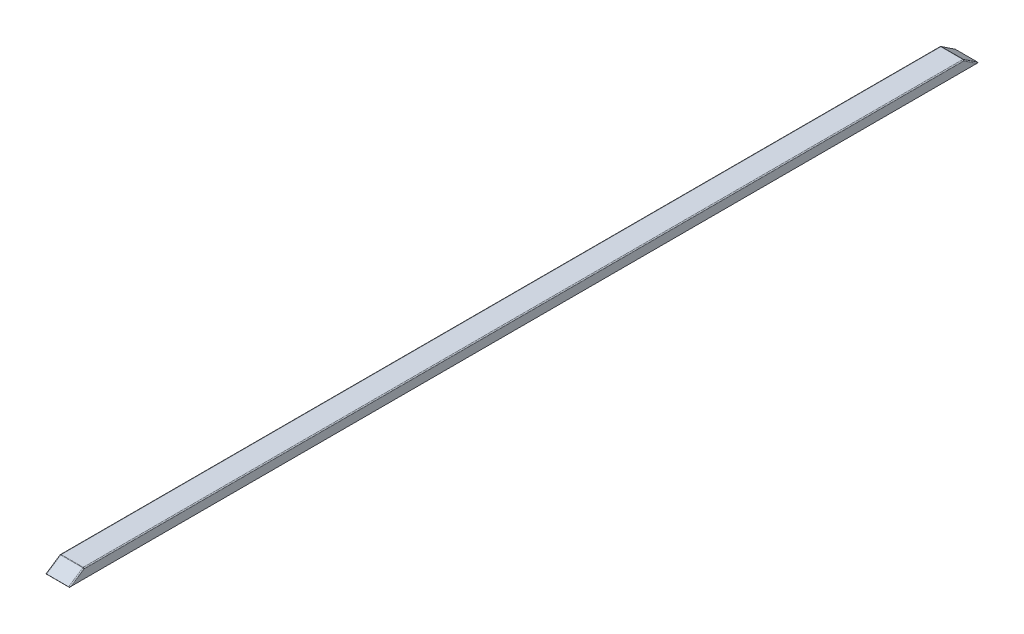
SolidWorks part; units mm, degrees
ref_plane "Front Plane" through (0, 0, 0) normal (0, 0, 1) x (1, 0, 0)
ref_plane "Top Plane" through (0, 0, 0) normal (0, 1, 0) x (1, 0, 0)
ref_plane "Right Plane" through (0, 0, 0) normal (1, 0, 0) x (0, 0, -1)
sketch "Sketch1" plane through (0, 0, 0) normal (0, 0, 1) x (1, 0, 0)
  line L0 (0, 0) -> (0, 20)
  line L1 (0, 20) -> (50, 20)
  line L2 (50, 20) -> (50, 0)
  line L3 (2, 0) -> (2, 18)
  line L4 (2, 18) -> (48, 18)
  line L5 (48, 18) -> (48, 0)
  line L6 (0, 0) -> (2, 0)
  line L7 (48, 0) -> (50, 0)
  dimension "D1" = 50
  dimension "D2" = 20
  dimension "D3" = 2
extrude "Boss-Extrude1" add sketch "Sketch1" along normal blind 1900
fillet "Fillet1" radius 2 4 edges at (48, 18, 950) (2, 18, 950) (0, 20, 950) (50, 20, 950)
sketch "Sketch2" plane through (50, 0, 0) normal (1, 0, 0) x (0, 0, -1)
  line L0 (0, 0) -> (-30, 20)
  line L1 (-1900, 20) -> (0, 20) construction
  line L2 (-30, 20) -> (0, 20)
  line L3 (0, 20) -> (0, 0)
  line L4 (-1900, 0) -> (-1870, 20)
  line L5 (-1870, 20) -> (-1900, 20)
  line L6 (-1900, 20) -> (-1900, 0)
  dimension "D1" = 30
  dimension "D2" = 30
extrude "Cut-Extrude1" cut sketch "Sketch2" against normal through all both and the other way through all
sketch "Sketch5" plane through (0, 0, 0) normal (0, 0.8321, -0.5547) x (1, 0, 0)
  line L0 (0, 0) -> (50, 0)
  line L8 (46, -32.45) -> (4, -32.45)
  line L9 (2, -28.8444) -> (2, 0)
  line L10 (2, 0) -> (0, 0)
  line L11 (0, 0) -> (0, -32.45)
  line L12 (2, -36.0555) -> (48, -36.0555)
  line L13 (50, -32.45) -> (50, 0)
  line L14 (50, 0) -> (48, 0)
  line L15 (48, 0) -> (48, -28.8444)
  line L19 (0, 0) -> (0, -32.45)
  line L20 (2, -36.0555) -> (48, -36.0555)
  line L21 (50, -32.45) -> (50, 0)
  ellipse E4 centre (46, -28.8444) end of major axis (46, -32.45) minor radius 2 (46, -32.45) -> (48, -28.8444) ccw
  ellipse E5 centre (4, -28.8444) end of major axis (4, -32.45) minor radius 2 (2, -28.8444) -> (4, -32.45) ccw
  ellipse E6 centre (2, -32.45) end of major axis (2, -28.8444) minor radius 2 (0, -32.45) -> (2, -36.0555) ccw
  ellipse E7 centre (48, -32.45) end of major axis (48, -28.8444) minor radius 2 (48, -36.0555) -> (50, -32.45) ccw
  ellipse E10 centre (2, -32.45) end of major axis (2, -28.8444) minor radius 2 (0, -32.45) -> (2, -36.0555) ccw
  ellipse E11 centre (48, -32.45) end of major axis (48, -28.8444) minor radius 2 (48, -36.0555) -> (50, -32.45) ccw
  dimension "D1" = 0
extrude "Boss-Extrude2" add sketch "Sketch5" against normal blind 1
sketch "Sketch6" plane through (0, 876.9231, 584.6154) normal (0, 0.8321, 0.5547) x (1, 0, 0)
  line L0 (0, -1580.8956) -> (50, -1580.8956)
  line L8 (48, -1580.8956) -> (50, -1580.8956)
  line L9 (50, -1580.8956) -> (50, -1548.4456)
  line L10 (48, -1544.84) -> (2, -1544.84)
  line L11 (0, -1548.4456) -> (0, -1580.8956)
  line L12 (0, -1580.8956) -> (2, -1580.8956)
  line L13 (2, -1580.8956) -> (2, -1552.0511)
  line L14 (4, -1548.4456) -> (46, -1548.4456)
  line L15 (48, -1552.0511) -> (48, -1580.8956)
  line L17 (50, -1580.8956) -> (50, -1548.4456)
  line L18 (48, -1544.84) -> (2, -1544.84)
  line L19 (0, -1548.4456) -> (0, -1580.8956)
  ellipse E4 centre (48, -1548.4456) end of major axis (48, -1544.84) minor radius 2 (50, -1548.4456) -> (48, -1544.84) ccw
  ellipse E5 centre (2, -1548.4456) end of major axis (2, -1544.84) minor radius 2 (2, -1544.84) -> (0, -1548.4456) ccw
  ellipse E6 centre (4, -1552.0511) end of major axis (4, -1555.6567) minor radius 2 (4, -1548.4456) -> (2, -1552.0511) ccw
  ellipse E7 centre (46, -1552.0511) end of major axis (46, -1555.6567) minor radius 2 (48, -1552.0511) -> (46, -1548.4456) ccw
  ellipse E8 centre (48, -1548.4456) end of major axis (48, -1544.84) minor radius 2 (50, -1548.4456) -> (48, -1544.84) ccw
  ellipse E9 centre (2, -1548.4456) end of major axis (2, -1544.84) minor radius 2 (2, -1544.84) -> (0, -1548.4456) ccw
  dimension "D1" = 0
extrude "Boss-Extrude3" add sketch "Sketch6" against normal blind 1
fillet "Fillet2" radius 2 5 edges at (0, 9, 1886.5) (0.5858, 19.4142, 1870.8787) (50, 9, 1886.5) (49.4142, 19.4142, 1870.8787) (25, 20, 1870)
fillet "Fillet3" radius 2 5 edges at (0, 9, 13.5) (0.5858, 19.4142, 29.1213) (50, 9, 13.5) (49.4142, 19.4142, 29.1213) (25, 20, 30)
equation "\"totalWidth\"=1930"
equation "\"D1@Boss-Extrude1\"= \"boxWidth\" - 30"
equation "\"CarBeamWidth\"=700.0"
equation "\"WheelWidth\"=650.0"
equation "\"Wheel_FrontBoxDistance\"=1390.0"
equation "\"boxLength\"=5100.0"
equation "\"boxWidth\"=1930.0"
equation "\"MetalSheet_3mm_length\"=5030.0"
equation "\"MetalSheet_3mm_width\"=1923.0"
equation "\"MetalSheet_3mm_FloorCut_L_length\"=1764.0"
equation "\"MetalSheet_3mm_FloorCut_L_disdance\"=1665.0"
equation "\"MetalSheet_3mm_FloorCut_R_length\"=1764.0"
equation "\"MetalSheet_3mm_FloorCut_R_disdance\"=1665.0"
equation "\"indoorHeight\"=1940.0"
equation "\"indoorHeight_para\"=25.0"
equation "\"rearLightHeight_para\"=265.0"
equation "\"doorColumnBar_A_FR_3mm_length_Cut\"=2310.0"
equation "\"A\"=0.0"
equation "\"haveDoor_R\"=1"
equation "\"side_door_bottom_R_3mm_length\"=1934.0"
equation "\"side_door_bottom_R_3mm_toFrontDistance\"=1583.0"
equation "\"1Bar_Side_RF_3mm_length\"=1493.0"
equation "\"1Bar_Side_RB_3mm_length\"=1493.0"
equation "\"DoorSeparator_RF_3mm_withHinge_toFrontDistance\"=1673.0"
equation "\"DoorSeparator_RF_3mm_withHinge_exist\"=1"
equation "\"DoorSeparator_RB_3mm_withHinge_toFrontDistance\"=3427.0"
equation "\"DoorSeparator_RB_3mm_withHinge_exist\"=1"
equation "\"Door_R1_L_open_Single_toFrontDistance\"=2547.5"
equation "\"Door_R1_L_open_Single_exist\"=1"
equation "\"door_base_long7_R1_L_open_Single_height\"=1890.0"
equation "\"door_base_short7_R1_L_open_Single_height\"=1890.0"
equation "\"door_base_short7_R1_L_open_Single_width\"=864"
equation "\"Door_R1_R_open_Single_toFrontDistance\"=3422.0"
equation "\"Door_R1_R_open_Single_exist\"=1"
equation "\"door_base_long7_R1_R_open_Single_height\"=1890.0"
equation "\"door_base_short7_R1_R_open_Single_height\"=1890.0"
equation "\"door_base_short7_R1_R_open_Single_width\"=864"
equation "\"x\"=66.0"
equation "\"door_base_double_BL_height\"=1890.0"
equation "\"door_base_short7_BL_Single_height\"=1890.0"
equation "\"door_base_short7_BL_Single_width\"=864"
equation "\"door_base_long7_BR_Single_height\"=1890.0"
equation "\"door_base_short7_BR_Single_height\"=1890.0"
equation "\"door_base_short7_BR_Single_width\"=864"
equation "\"da\"=62.0"
equation "\"SquareTube_length\"=1923.0"
equation "\"channelSteel_length\"=5030.0"
equation "\"SquareTube_inFront_AvgDistance\"=285.0"
equation "\"SquareTube_inFront_TotalCount\"=5"
equation "\"SquareTube_inFront1_cutDepth50_R\"=0.5"
equation "\"SquareTube_inFront1_cutDepth50_L\"=0.5"
equation "\"SquareTube_inFront2_cutDepth50_R\"=0.5"
equation "\"SquareTube_inFront2_cutDepth50_L\"=0.5"
equation "\"SquareTube_inFront3_cutDepth50_R\"=0.5"
equation "\"SquareTube_inFront3_cutDepth50_L\"=0.5"
equation "\"SquareTube_inFront4_cutDepth50_R\"=0.5"
equation "\"SquareTube_inFront4_cutDepth50_L\"=0.5"
equation "\"SquareTube_inFront5_cutDepth50_R\"=50"
equation "\"SquareTube_inFront5_cutDepth50_L\"=50"
equation "\"SquareTube_inFront6_cutDepth50_R\"=50"
equation "\"SquareTube_inFront6_cutDepth50_L\"=50"
equation "\"SquareTube_inFront7_cutDepth50_R\"=50"
equation "\"SquareTube_inFront7_cutDepth50_L\"=50"
equation "\"SquareTube_inFront8_cutDepth50_R\"=50"
equation "\"SquareTube_inFront8_cutDepth50_L\"=50"
equation "\"SquareTube_inFront9_cutDepth50_R\"=50"
equation "\"SquareTube_inFront9_cutDepth50_L\"=50"
equation "\"SquareTube_inFront10_cutDepth50_R\"=50"
equation "\"SquareTube_inFront10_cutDepth50_L\"=50"
equation "\"SquareTube_inFront11_cutDepth50_R\"=50"
equation "\"SquareTube_inFront11_cutDepth50_L\"=50"
equation "\"SquareTube_inFront12_cutDepth50_R\"=50"
equation "\"SquareTube_inFront12_cutDepth50_L\"=50"
equation "\"SquareTube_inFront13_cutDepth50_R\"=50"
equation "\"SquareTube_inFront13_cutDepth50_L\"=50"
equation "\"SquareTube_inFront14_cutDepth50_R\"=50"
equation "\"SquareTube_inFront14_cutDepth50_L\"=50"
equation "\"SquareTube_inBack_AvgDistance\"=333.125"
equation "\"SquareTube_inBack_TotalCount\"=9"
equation "\"SquareTube_inBack1_cutDepth50_R\"=50"
equation "\"SquareTube_inBack1_cutDepth50_L\"=50"
equation "\"SquareTube_inBack2_cutDepth50_R\"=50"
equation "\"SquareTube_inBack2_cutDepth50_L\"=50"
equation "\"SquareTube_inBack3_cutDepth50_R\"=50"
equation "\"SquareTube_inBack3_cutDepth50_L\"=50"
equation "\"SquareTube_inBack4_cutDepth50_R\"=50"
equation "\"SquareTube_inBack4_cutDepth50_L\"=50"
equation "\"SquareTube_inBack5_cutDepth50_R\"=50"
equation "\"SquareTube_inBack5_cutDepth50_L\"=50"
equation "\"SquareTube_inBack6_cutDepth50_R\"=0.5"
equation "\"SquareTube_inBack6_cutDepth50_L\"=0.5"
equation "\"SquareTube_inBack7_cutDepth50_R\"=0.5"
equation "\"SquareTube_inBack7_cutDepth50_L\"=0.5"
equation "\"SquareTube_inBack8_cutDepth50_R\"=0.5"
equation "\"SquareTube_inBack8_cutDepth50_L\"=0.5"
